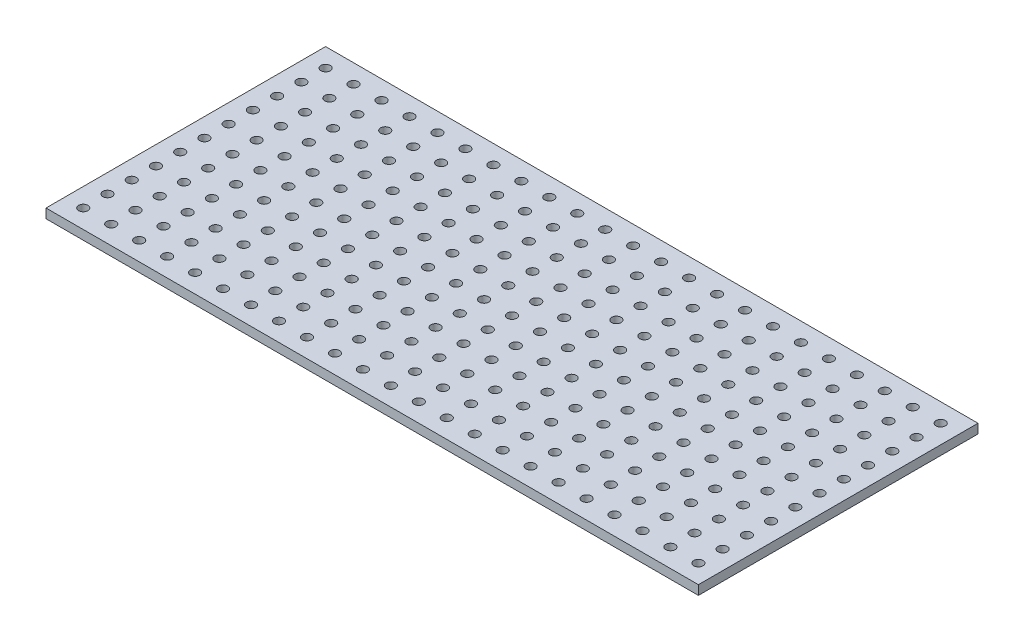
SolidWorks part; units mm, degrees
ref_plane "Alzado" through (0, 0, 0) normal (0, 0, 1) x (1, 0, 0)
ref_plane "Planta" through (0, 0, 0) normal (0, 1, 0) x (1, 0, 0)
ref_plane "Vista lateral" through (0, 0, 0) normal (1, 0, 0) x (0, 0, -1)
sketch "Croquis2" plane through (0, 0, 0) normal (0, 1, 0) x (1, 0, 0)
  line L1 (-350, -150) -> (350, -150)
  line L2 (-350, -150) -> (-350, 150)
  line L3 (-350, 150) -> (350, 150)
  line L4 (350, -150) -> (350, 150)
  line L5 (-350, -150) -> (350, 150) construction
  line L6 (-350, 150) -> (350, -150) construction
  point P0 (0, 0)
  dimension "D1" = 700
  dimension "D2" = 300
extrude "Saliente-Extruir1" add sketch "Croquis2" along normal blind 10
sketch "Croquis3" plane through (0, 10, 0) normal (0, 1, 0) x (1, 0, 0)
  line L0 (-350, 150) -> (-350, -150) construction
  line L1 (350, 150) -> (-350, 150) construction
  circle A0 centre (-330, 130) radius 5
  dimension "D1" = 10
  dimension "D2" = 20
  dimension "D3" = 20
extrude "Cortar-Extruir1" cut sketch "Croquis3" against normal up to surface (10 mm away) up to face at (0, 0, 0)
pattern_linear "MatrizL1" count 11 spacing 26 along (0, 0, 1) count 23 spacing 30 along (1, 0, 0) of "Cortar-Extruir1"
